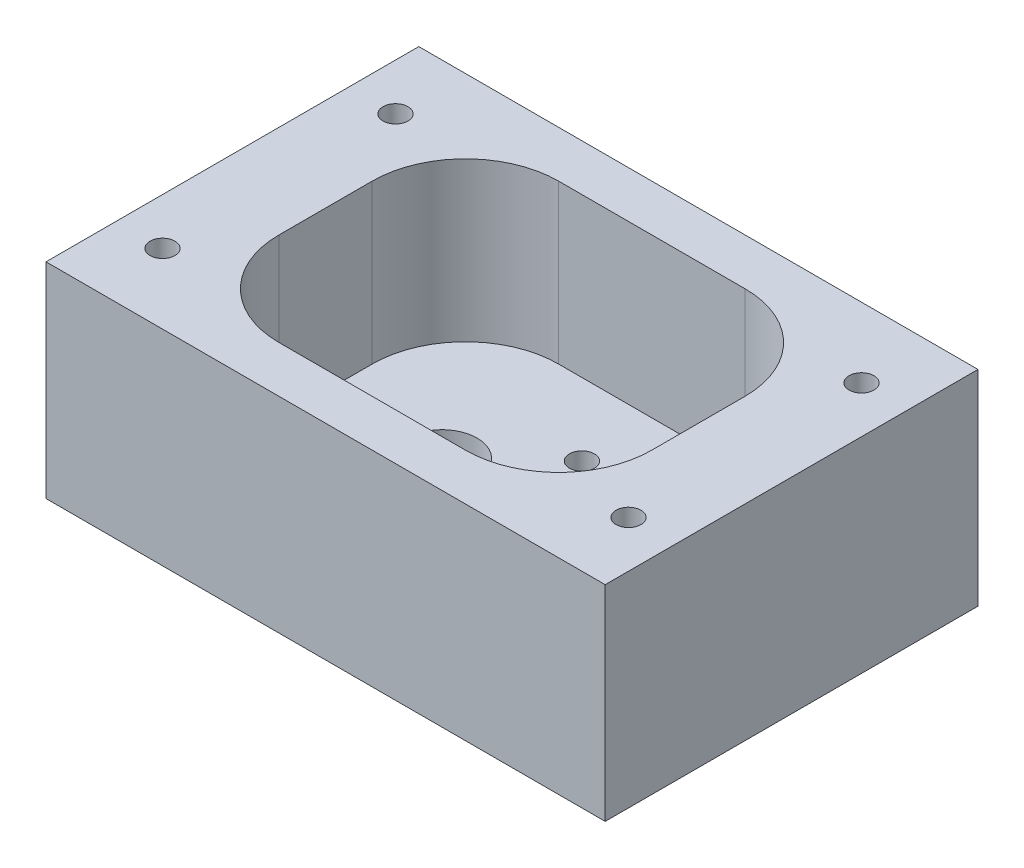
SolidWorks part; units mm, degrees
material "6061 Alloy"
ref_plane "Front Plane" through (0, 0, 0) normal (0, 0, 1) x (1, 0, 0)
ref_plane "Top Plane" through (0, 0, 0) normal (0, 1, 0) x (1, 0, 0)
ref_plane "Right Plane" through (0, 0, 0) normal (1, 0, 0) x (0, 0, -1)
sketch "Sketch1" plane through (0, 0, 0) normal (0, 1, 0) x (1, 0, 0)
  line L1 (-38.1, -25.4) -> (38.1, -25.4)
  line L2 (-38.1, -25.4) -> (-38.1, 25.4)
  line L3 (-38.1, 25.4) -> (38.1, 25.4)
  line L4 (38.1, -25.4) -> (38.1, 25.4)
  line L5 (-38.1, -25.4) -> (38.1, 25.4) construction
  line L6 (-38.1, 25.4) -> (38.1, -25.4) construction
  point P0 (0, 0)
  dimension "D1" = 76.2
  dimension "D2" = 50.8
extrude "Boss-Extrude1" add sketch "Sketch1" along normal blind 27.94
sketch "Sketch2" plane through (0, 0, 0) normal (0, -1, 0) x (1, 0, 0)
  line L0 (-38.1, 0) -> (38.1, 0) construction
  line L1 (-38.1, -25.4) -> (-38.1, 25.4) construction
  line L2 (38.1, 25.4) -> (38.1, -25.4) construction
  line L3 (0, 25.4) -> (0, -25.4) construction
  line L4 (-38.1, 25.4) -> (38.1, 25.4) construction
  line L5 (38.1, -25.4) -> (-38.1, -25.4) construction
  circle A0 centre (-9.525, 0) radius 4.7625
  circle A1 centre (9.525, 0) radius 9
  point P12 (-9.525, 0)
  point P13 (9.525, 0)
  dimension "D3" = 18
  dimension "D4" = 9.525
  dimension "D1" = 19.05
  dimension "D2" = 9.525
extrude "Cut-Extrude1" cut sketch "Sketch2" against normal through all contours A0 | A1
sketch "Sketch3" plane through (0, 27.94, 0) normal (0, 1, 0) x (1, 0, 0)
  line L0 (9.525, 0) -> (-9.525, 0) construction
  line L1 (-12.7, -19.05) -> (12.7, -19.05)
  line L2 (-25.4, -6.35) -> (-25.4, 6.35)
  line L3 (-12.7, 19.05) -> (12.7, 19.05)
  line L4 (25.4, -6.35) -> (25.4, 6.35)
  line L5 (-25.4, -19.05) -> (25.4, 19.05) construction
  line L6 (-25.4, 19.05) -> (25.4, -19.05) construction
  arc A0 (12.7, 19.05) -> (25.4, 6.35) centre (12.7, 6.35) cw
  arc A1 (25.4, -6.35) -> (12.7, -19.05) centre (12.7, -6.35) cw
  arc A2 (-12.7, -19.05) -> (-25.4, -6.35) centre (-12.7, -6.35) cw
  arc A3 (-25.4, 6.35) -> (-12.7, 19.05) centre (-12.7, 6.35) cw
  point P0 (0, 0)
  dimension "D3" = 12.7
  dimension "D1" = 38.1
  dimension "D2" = 50.8
extrude "Cut-Extrude2" cut sketch "Sketch3" against normal blind 21.59
sketch "Sketch4" plane through (0, 0, 0) normal (0, -1, 0) x (1, 0, 0)
  line L0 (-31.75, 25.4) -> (-31.75, -25.4) construction
  line L1 (-38.1, 25.4) -> (38.1, 25.4) construction
  line L2 (38.1, -25.4) -> (-38.1, -25.4) construction
  line L3 (31.75, 25.4) -> (31.75, -25.4) construction
  line L4 (-38.1, -25.4) -> (-38.1, 25.4) construction
  line L5 (38.1, 25.4) -> (38.1, -25.4) construction
  line L6 (-31.75, 0) -> (31.75, 0) construction
  line L7 (0.3326, 9.1924) -> (18.7174, -9.1924) construction
  line L8 (18.7174, 9.1924) -> (0.3326, -9.1924) construction
  circle A1 centre (9.525, 0) radius 9 construction
  point P12 (-31.75, 15.875)
  point P13 (-31.75, -15.875)
  point P14 (31.75, 15.875)
  point P15 (31.75, -15.875)
  point P20 (9.525, 0)
  point P25 (9.525, 0)
  point P27 (0.3326, 9.1924)
  point P28 (18.7174, 9.1924)
  point P29 (18.7174, -9.1924)
  point P30 (0.3326, -9.1924)
  dimension "D1" = 6.35
  dimension "D2" = 6.35
  dimension "D3" = 31.75
  dimension "D4" = 45
  dimension "D5" = 45
  dimension "D6" = 26
hole_wizard "M3 Clearance Hole1" positions "3DSketch1" profile "Sketch5" hole size "M3" standard "ANSI Metric" end condition through all
sketch3d "3DSketch1"
  point P0 (-31.75, 0, 15.875)
  point P3 (-31.75, 0, -15.875)
  point P6 (0.3326, 0, 9.1924)
  point P9 (0.3326, 0, -9.1924)
  point P12 (18.7174, 0, 9.1924)
  point P15 (18.7174, 0, -9.1924)
  point P18 (31.75, 0, 15.875)
  point P21 (31.75, 0, -15.875)
sketch "Sketch5" plane through (-31.75, 0, 15.875) normal (1, 0, 0) x (0, 0, -1)
  line L0 (0, 0) -> (0, 27.94)
  line L1 (0, 27.94) -> (1.7, 27.94)
  line L2 (1.7, 27.94) -> (1.7, 0)
  line L5 (1.7, 0) -> (0, 0)
  line L11 (0, -6.35) -> (0, 107.95) construction
  dimension "Thru Hole Dia." = 3.4
  dimension "Thru Hole Depth" = 27.94
equation "\"D2@Sketch4\"=\"D1@Sketch4\""
equation "\"D2@Sketch2\"=\"D1@Sketch2\"/2"
